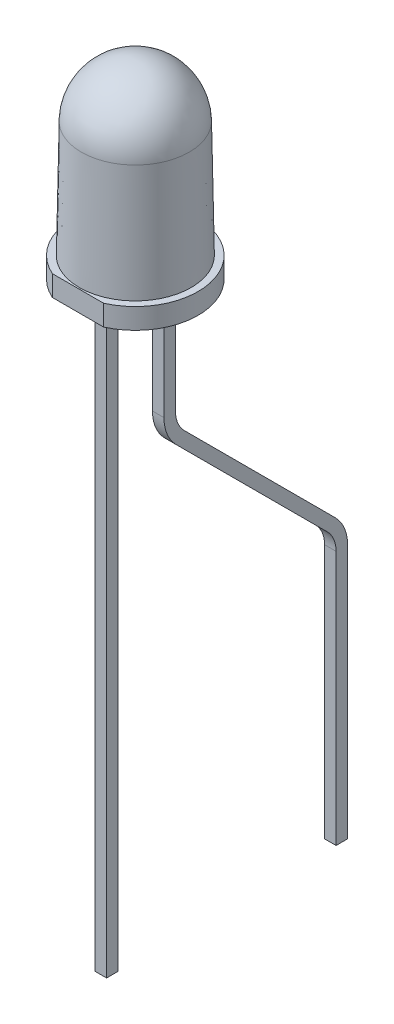
SolidWorks part; units mm, degrees
ref_plane "Front Plane" through (0, 0, 0) normal (0, 0, 1) x (1, 0, 0)
ref_plane "Top Plane" through (0, 0, 0) normal (0, 1, 0) x (1, 0, 0)
ref_plane "Right Plane" through (0, 0, 0) normal (1, 0, 0) x (0, 0, -1)
sketch "Sketch1" plane through (0, 0, 0) normal (1, 0, 0) x (0, 0, -1)
  line L0 (0, 8.4074) -> (0, 0)
  line L1 (0, 0) -> (2.7813, 0)
  line L2 (2.4765, 0.9144) -> (2.3876, 6.0607)
  line L3 (2.4765, 0.9144) -> (2.7813, 0.9144)
  line L4 (2.7813, 0.9144) -> (2.7813, 0)
  arc A0 (2.3876, 6.0607) -> (0, 8.4074) centre (0, 6.0194) ccw
  dimension "D1" = 2.4765
  dimension "D2" = 2.3876
  dimension "D3" = 7.493
  dimension "D4" = 2.7813
  dimension "D5" = 0.9144
revolve "Revolve1" add sketch "Sketch1" angle 360 about L0
ref_plane "Plane1" through (0, 0, 2.54) normal (0, 0, 1) x (1, 0, 0)
sketch "Sketch2" plane through (0, 0, 2.54) normal (0, 0, 1) x (1, 0, 0)
  line L1 (-4.7358, 11.252) -> (3.4904, 11.252)
  line L2 (-4.7358, 11.252) -> (-4.7358, -1.5294)
  line L3 (-4.7358, -1.5294) -> (3.4904, -1.5294)
  line L4 (3.4904, 11.252) -> (3.4904, -1.5294)
extrude "Extrude1" cut sketch "Sketch2" along normal through all
sketch "Sketch3" plane through (0, 0, 0) normal (1, 0, 0) x (0, 0, -1)
  line L0 (-1.27, 0) -> (-1.27, -25.908)
  line L1 (-2.54, 0) -> (2.7813, 0) construction
  dimension "D1" = 1.27
  dimension "D2" = 25.908
sketch "Sketch5" plane through (0, 0, 0) normal (1, 0, 0) x (0, 0, -1)
  line L0 (1.27, 0) -> (1.27, -5.6924)
  line L1 (-2.54, 0) -> (2.7813, 0) construction
  line L2 (1.735, -6.815) -> (8.425, -13.505)
  line L3 (8.89, -14.6276) -> (8.89, -25.908)
  line L4 (-1.27, 0) -> (-1.27, -25.908) construction
  arc A0 (1.27, -5.6924) -> (1.735, -6.815) centre (2.8575, -5.6924) ccw
  arc A1 (8.425, -13.505) -> (8.89, -14.6276) centre (7.3025, -14.6276) cw
  point P12 (1.27, -6.35)
  dimension "D5" = 1.5875
  dimension "D1" = 6.35
  dimension "D2" = 45
  dimension "D3" = 1.27
  dimension "D4" = 10.16
sketch "Sketch6" plane through (0, 0, 0) normal (0, 1, 0) x (1, 0, 0)
  line L0 (-0.254, -1.524) -> (0.254, -1.016) construction
  line L1 (0.254, -1.524) -> (-0.254, -1.524)
  line L2 (0.254, -1.524) -> (0.254, -1.016)
  line L3 (0.254, -1.016) -> (-0.254, -1.016)
  line L4 (-0.254, -1.524) -> (-0.254, -1.016)
  dimension "D1" = 0.508
  dimension "D2" = 0.508
extrude "Extrude2" add sketch "Sketch6" against normal up to vertex up to point (0, -25.908, 1.27)
sketch "Sketch7" plane through (0, 0, 0) normal (0, 1, 0) x (1, 0, 0)
  line L0 (-0.254, 1.016) -> (0.254, 1.524) construction
  line L1 (0.254, 1.016) -> (-0.254, 1.016)
  line L2 (0.254, 1.016) -> (0.254, 1.524)
  line L3 (0.254, 1.524) -> (-0.254, 1.524)
  line L4 (-0.254, 1.016) -> (-0.254, 1.524)
  dimension "D1" = 0.508
  dimension "D2" = 0.508
sweep "Sweep1" add profiles "Sketch7" path "Sketch5"
ref_axis "Centerline" through (0, -14.2433, 0) along (0, 1, 0)
